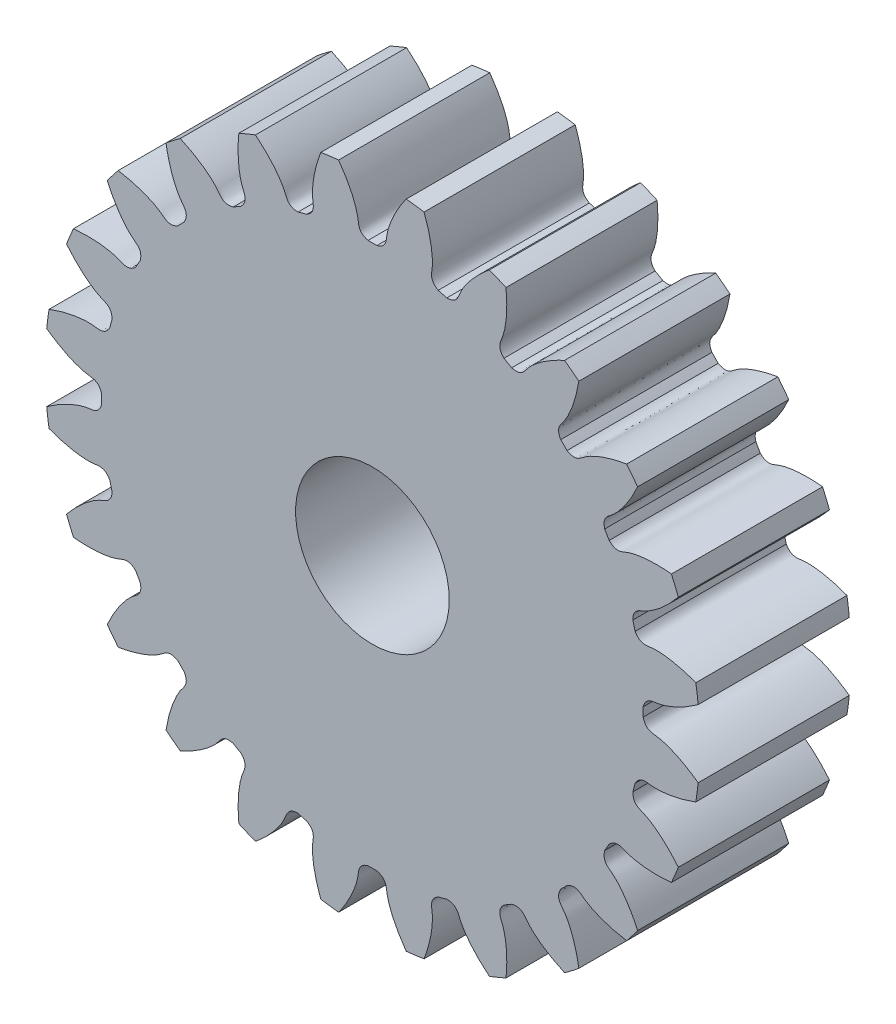
SolidWorks part; units mm, degrees
ref_plane "前视基准面" through (0, 0, 0) normal (0, 0, 1) x (1, 0, 0)
ref_plane "上视基准面" through (0, 0, 0) normal (0, 1, 0) x (1, 0, 0)
ref_plane "右视基准面" through (0, 0, 0) normal (1, 0, 0) x (0, 0, -1)
sketch "草图1" plane through (0, 0, 0) normal (0, 0, 1) x (1, 0, 0)
  circle A0 centre (0, 0) radius 6.5
extrude "凸台-拉伸1" add sketch "草图1" along normal blind 3
ref_axis "基准轴1" through (0, 0, 3) along (0, 0, -1)
sketch "草图2" plane through (0, 0, 0) normal (0, 0, 1) x (1, 0, 0)
  line L0 (0, 0) -> (0, 6.5) construction
  circle A0 centre (0, 0) radius 6.5 construction
  arc A1 (0.0884, 5.3743) -> (-0.0884, 5.3743) centre (0, 0) ccw
  arc A2 (1.5578, 7.3471) -> (-1.5578, 7.3471) centre (0, 0) ccw
  spline S0 degree 3 poles (0.0884, 5.3743) (0.284, 5.4284) (0.2695, 5.5579) (0.2931, 5.6863) (0.2965, 5.7029) (0.3007, 5.7216) (0.3058, 5.7424) (0.312, 5.7653) (0.3191, 5.7902) (0.3275, 5.8171) (0.3371, 5.846) (0.348, 5.8769) (0.3604, 5.9096) (0.3742, 5.9441) (0.3896, 5.9805) (0.4067, 6.0185) (0.4254, 6.0583) (0.446, 6.0997) (0.4684, 6.1427) (0.4928, 6.1872) (0.5192, 6.2332) (0.5476, 6.2806) (0.5782, 6.3293) (0.611, 6.3792) (0.6461, 6.4304) (0.6834, 6.4827) (0.7232, 6.536) (0.7654, 6.5903) (0.8101, 6.6456) (0.8574, 6.7016) (0.9073, 6.7583) (0.9598, 6.8158) (1.015, 6.8738) (1.0729, 6.9322) (1.1336, 6.9911) (1.1972, 7.0503) (1.2635, 7.1097) (1.3328, 7.1693) (1.4302, 7.2497) (1.506, 7.3084) (1.5578, 7.3471) knots 0 0 0 0 0.143961 0.149818 0.156577 0.164236 0.172796 0.182258 0.19262 0.203884 0.216049 0.229115 0.243082 0.25795 0.273719 0.290389 0.30796 0.326433 0.345806 0.366081 0.387257 0.409333 0.432311 0.45619 0.48097 0.506651 0.533234 0.560717 0.589101 0.618387 0.648574 0.679661 0.71165 0.74454 0.778331 0.813023 0.848616 0.885111 0.922506 1 1 1 1
  spline S1 degree 3 poles (-0.0884, 5.3743) (-0.284, 5.4284) (-0.2695, 5.5579) (-0.2931, 5.6863) (-0.2965, 5.7029) (-0.3007, 5.7216) (-0.3058, 5.7424) (-0.312, 5.7653) (-0.3191, 5.7902) (-0.3275, 5.8171) (-0.3371, 5.846) (-0.348, 5.8769) (-0.3604, 5.9096) (-0.3742, 5.9441) (-0.3896, 5.9805) (-0.4067, 6.0185) (-0.4254, 6.0583) (-0.446, 6.0997) (-0.4684, 6.1427) (-0.4928, 6.1872) (-0.5192, 6.2332) (-0.5476, 6.2806) (-0.5782, 6.3293) (-0.611, 6.3792) (-0.6461, 6.4304) (-0.6834, 6.4827) (-0.7232, 6.536) (-0.7654, 6.5903) (-0.8101, 6.6456) (-0.8574, 6.7016) (-0.9073, 6.7583) (-0.9598, 6.8158) (-1.015, 6.8738) (-1.0729, 6.9322) (-1.1336, 6.9911) (-1.1972, 7.0503) (-1.2635, 7.1097) (-1.3328, 7.1693) (-1.4302, 7.2497) (-1.506, 7.3084) (-1.5578, 7.3471) knots 0 0 0 0 0.143961 0.149818 0.156577 0.164236 0.172796 0.182258 0.19262 0.203884 0.216049 0.229115 0.243082 0.25795 0.273719 0.290389 0.30796 0.326433 0.345806 0.366081 0.387257 0.409333 0.432311 0.45619 0.48097 0.506651 0.533234 0.560717 0.589101 0.618387 0.648574 0.679661 0.71165 0.74454 0.778331 0.813023 0.848616 0.885111 0.922506 1 1 1 1
extrude "切除-拉伸1" cut sketch "草图2" along normal through all
pattern_circular "阵列(圆周)1" count 24 over 360 about axis through (0, 0, 3) along (0, 0, -1) of "切除-拉伸1"
sketch "草图3" plane through (0, 0, 0) normal (0, 0, 1) x (1, 0, 0)
  circle A0 centre (0, 0) radius 6 construction
  dimension "Dn" = 12
sketch "草图4" plane through (0, 0, 3) normal (0, 0, 1) x (1, 0, 0)
  circle A0 centre (0, 0) radius 1.525
  dimension "D1" = 3.05
extrude "切除-拉伸2" cut sketch "草图4" against normal up to next
